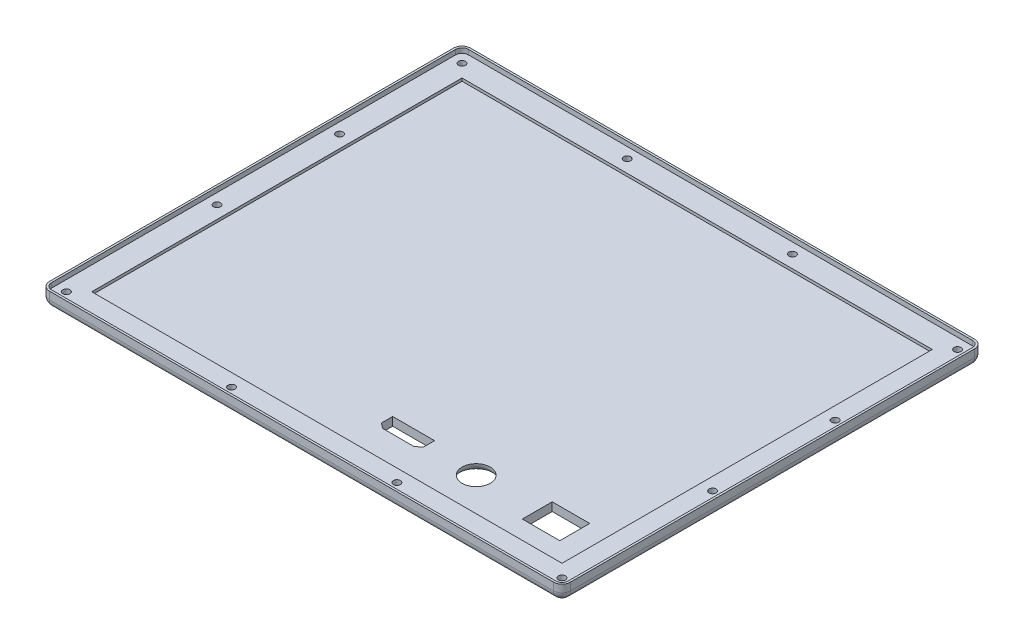
SolidWorks part; units mm, degrees
ref_plane "Front Plane" through (0, 0, 0) normal (0, 0, 1) x (1, 0, 0)
ref_plane "Top Plane" through (0, 0, 0) normal (0, 1, 0) x (1, 0, 0)
ref_plane "Right Plane" through (0, 0, 0) normal (1, 0, 0) x (0, 0, -1)
sketch "Sketch1" plane through (0, 0, 0) normal (0, 1, 0) x (1, 0, 0)
  line L1 (0, 0) -> (164.87, 0)
  line L2 (0, 0) -> (0, -104.3)
  line L3 (0, -104.3) -> (164.87, -104.3)
  line L4 (164.87, 0) -> (164.87, -104.3)
  line L5 (7.23, -7.46) -> (162.2, -7.46)
  line L6 (7.23, -7.46) -> (7.23, -101.93)
  line L7 (7.23, -101.93) -> (162.2, -101.93)
  line L8 (162.2, -7.46) -> (162.2, -101.93)
  line L9 (-4.77, 7.54) -> (174.2, 7.54)
  line L10 (-7.77, 4.54) -> (-7.77, -138.93)
  line L11 (-4.77, -141.93) -> (174.2, -141.93)
  line L12 (177.2, 4.54) -> (177.2, -138.93)
  arc A0 (174.2, -141.93) -> (177.2, -138.93) centre (174.2, -138.93) ccw
  arc A1 (-7.77, -138.93) -> (-4.77, -141.93) centre (-4.77, -138.93) ccw
  arc A2 (-4.77, 7.54) -> (-7.77, 4.54) centre (-4.77, 4.54) ccw
  arc A3 (174.2, 7.54) -> (177.2, 4.54) centre (174.2, 4.54) cw
  dimension "D11" = 3
  dimension "D1" = 104.3
  dimension "D2" = 164.87
  dimension "D3" = 2.67
  dimension "D4" = 2.37
  dimension "D5" = 7.46
  dimension "D6" = 7.23
  dimension "D7" = 15
  dimension "D8" = 15
  dimension "D9" = 15
  dimension "D10" = 40
extrude "Boss-Extrude1" add sketch "Sketch1" against normal blind 1 contours A3 L9 A2 L10 A1 L11 A0 L12 L1 L4 L3 L2 | L4 L1 L2 L3 L5 L8 L7 L6 | L8 L5 L6 L7 region at (82.435, 0, 1.9509) region at (84.715, 0, 54.695) region at (84.715, 0, -5.1619)
sketch "Sketch12" plane through (0, -1, 0) normal (0, -1, 0) x (1, 0, 0)
  line L0 (-4.77, -7.54) -> (174.2, -7.54)
  line L1 (177.2, -4.54) -> (177.2, 138.93)
  line L2 (-4.77, 141.93) -> (174.2, 141.93)
  line L3 (-7.77, -4.54) -> (-7.77, 138.93)
  line L4 (176.45, -4.54) -> (176.45, 138.93)
  line L5 (-4.77, 141.18) -> (174.2, 141.18)
  line L6 (-7.02, -4.54) -> (-7.02, 138.93)
  line L7 (-4.77, -6.79) -> (174.2, -6.79)
  line L8 (176.2, -4.54) -> (176.2, 138.93)
  line L9 (-4.77, -6.54) -> (174.2, -6.54)
  line L10 (176.2, -4.54) -> (176.2, 138.93)
  line L11 (-4.77, -6.54) -> (174.2, -6.54)
  line L18 (-6.77, -4.54) -> (-6.77, 138.93)
  line L19 (-4.77, 140.93) -> (174.2, 140.93)
  line L20 (-6.77, -4.54) -> (-6.77, 138.93)
  line L21 (-4.77, 140.93) -> (174.2, 140.93)
  arc A0 (174.2, -7.54) -> (177.2, -4.54) centre (174.2, -4.54) ccw
  arc A1 (177.2, 138.93) -> (174.2, 141.93) centre (174.2, 138.93) ccw
  arc A2 (-4.77, 141.93) -> (-7.77, 138.93) centre (-4.77, 138.93) ccw
  arc A3 (-7.77, -4.54) -> (-4.77, -7.54) centre (-4.77, -4.54) ccw
  arc A4 (176.45, 138.93) -> (174.2, 141.18) centre (174.2, 138.93) ccw
  arc A5 (-4.77, 141.18) -> (-7.02, 138.93) centre (-4.77, 138.93) ccw
  arc A6 (176.2, 138.93) -> (174.2, 140.93) centre (174.2, 138.93) ccw
  arc A7 (174.2, -6.54) -> (176.2, -4.54) centre (174.2, -4.54) ccw
  arc A8 (176.2, 138.93) -> (174.2, 140.93) centre (174.2, 138.93) ccw
  arc A9 (174.2, -6.54) -> (176.2, -4.54) centre (174.2, -4.54) ccw
  arc A10 (-7.02, -4.54) -> (-4.77, -6.79) centre (-4.77, -4.54) ccw
  arc A11 (174.2, -6.79) -> (176.45, -4.54) centre (174.2, -4.54) ccw
  arc A14 (-6.77, -4.54) -> (-4.77, -6.54) centre (-4.77, -4.54) ccw
  arc A15 (-4.77, 140.93) -> (-6.77, 138.93) centre (-4.77, 138.93) ccw
  arc A16 (-6.77, -4.54) -> (-4.77, -6.54) centre (-4.77, -4.54) ccw
  arc A17 (-4.77, 140.93) -> (-6.77, 138.93) centre (-4.77, 138.93) ccw
  arc M25 (174.2, -7.54) -> (177.2, -4.54) centre (174.2, -4.54) ccw
  line M26 (177.2, -4.54) -> (177.2, 138.93)
  arc M27 (177.2, 138.93) -> (174.2, 141.93) centre (174.2, 138.93) ccw
  line M28 (174.2, 141.93) -> (-4.77, 141.93)
  arc M29 (-4.77, 141.93) -> (-7.77, 138.93) centre (-4.77, 138.93) ccw
  line M30 (-7.77, 138.93) -> (-7.77, -4.54)
  arc M31 (-7.77, -4.54) -> (-4.77, -7.54) centre (-4.77, -4.54) ccw
  line M32 (-4.77, -7.54) -> (174.2, -7.54)
  dimension "D1" = 1
  dimension "D2" = 1
  dimension "D3" = 1
  dimension "D4" = 0.25
sketch "Sketch8" plane through (0, -1, 0) normal (0, -1, 0) x (1, 0, 0)
  line L0 (177.2, -4.54) -> (177.2, 138.93) construction
  line L1 (86.11, 110.85) -> (164.87, 110.85)
  line L2 (86.11, 110.85) -> (86.11, 129.3)
  line L3 (86.11, 129.3) -> (164.87, 129.3)
  line L4 (164.87, 110.85) -> (164.87, 129.3)
  line L5 (-4.77, 141.93) -> (174.2, 141.93) construction
  dimension "D1" = 78.76
  dimension "D2" = 18.45
  dimension "D3" = 12.33
  dimension "D4" = 12.63
sketch "Sketch2" plane through (0, -1, 0) normal (0, -1, 0) x (1, 0, 0)
  line L0 (-7.77, -4.54) -> (-7.77, 138.93) construction
  line L1 (-4.77, -7.54) -> (174.2, -7.54) construction
  line L2 (177.2, -4.54) -> (177.2, 138.93) construction
  line L3 (-4.77, 141.93) -> (174.2, 141.93) construction
  circle A0 centre (-3.27, -3.04) radius 1.25
  circle A1 centre (172.7, -3.04) radius 1.25
  circle A2 centre (172.7, 137.43) radius 1.25
  circle A3 centre (-3.27, 137.43) radius 1.25
  circle A4 centre (-3.27, 40.45) radius 1.25
  circle A5 centre (-3.27, 83.94) radius 1.25
  circle A6 centre (172.7, 40.45) radius 1.25
  circle A7 centre (172.7, 83.94) radius 1.25
  circle A8 centre (114.05, -3.04) radius 1.25
  circle A9 centre (55.38, -3.04) radius 1.25
  circle A10 centre (114.05, 137.43) radius 1.25
  circle A11 centre (55.38, 137.43) radius 1.25
  dimension "D1" = 2.5
  dimension "D4" = 2.5
  dimension "D6" = 2.5
  dimension "D8" = 2.5
  dimension "D9" = 2.5
  dimension "D10" = 2.5
  dimension "D13" = 2.5
  dimension "D14" = 2.5
  dimension "D17" = 2.5
  dimension "D18" = 2.5
  dimension "D19" = 2.5
  dimension "D20" = 2.5
  dimension "D2" = 4.5
  dimension "D3" = 4.5
  dimension "D5" = 4.5
  dimension "D7" = 4.5
  dimension "D11" = 43.49
  dimension "D12" = 43.49
  dimension "D21" = 58.65
  dimension "D22" = 58.65
extrude "Cut-Extrude3" cut sketch "Sketch2" against normal up to next contours A1 | A8 | A0 | A5 | A3 | A11 | A10 | A2 | A7 | A6 | A9 | A4 region at (-3.27, -1, -3.04) region at (172.7, -1, -3.04) region at (172.7, -1, 137.43) region at (-3.27, -1, 137.43) region at (-3.27, -1, 83.94) region at (172.7, -1, 40.45) region at (172.7, -1, 83.94) region at (114.05, -1, -3.04) region at (114.05, -1, 137.43) region at (55.38, -1, 137.43)
extrude "Boss-Extrude2" add sketch "Sketch12" against normal blind 1.7 from surface contours A11 L7 A10 L6 A5 L5 A4 L4 M32 M25 M26 M27 M28 M29 M30 M31 region at (-6.7232, -1, -6.4932) starting at face at (172.7, 0, 85.19)
sketch "Sketch13" plane through (0, -1, 0) normal (0, -1, 0) x (1, 0, 0)
  line L0 (-4.77, -7.54) -> (174.2, -7.54) construction
  line L1 (168.2, 1.46) -> (1.23, 1.46)
  line L2 (168.2, 1.46) -> (168.2, 132.93)
  line L3 (168.2, 132.93) -> (1.23, 132.93)
  line L4 (1.23, 1.46) -> (1.23, 132.93)
  line L5 (177.2, -4.54) -> (177.2, 138.93) construction
  line L6 (-4.77, 141.93) -> (174.2, 141.93) construction
  line L7 (-7.77, -4.54) -> (-7.77, 138.93) construction
  dimension "D1" = 9
  dimension "D2" = 9
  dimension "D3" = 9
  dimension "D4" = 9
extrude "Cut-Extrude4" cut sketch "Sketch13" against normal up to next
extrude "Boss-Extrude3" add sketch "Sketch1<4>" against normal blind 3 from surface contours A3 L9 A2 L10 A1 L11 A0 L12 L1 L4 L3 L2 | L4 L1 L2 L3 L5 L8 L7 L6 | L8 L5 L6 L7 region at (82.435, 0, 1.9509) region at (84.715, 0, 54.695) region at (84.715, 0, -5.1619) starting at face at (84.715, -1, 67.195)
sketch "Sketch1<4>" plane through (0, 0, 0) normal (0, 1, 0) x (1, 0, 0) same geometry as "Sketch1"
fillet "Fillet1" radius 3 8 edges at (176.3213, -4, -6.6613) (84.715, -4, -7.54) (-6.8913, -4, -6.6613) (-7.77, -4, 67.195) (-6.8913, -4, 141.0513) (84.715, -4, 141.93) (176.3213, -4, 141.0513) (177.2, -4, 67.195)
sketch "Sketch15" plane through (0, -4, 0) normal (0, -1, 0) x (1, 0, 0)
  line L0 (106.87, 116.85) -> (92.01, 116.85)
  line L1 (86.11, 110.85) -> (164.87, 110.85) construction
  line L2 (92.01, 116.85) -> (92.01, 120.92)
  line L3 (164.87, 110.85) -> (164.87, 129.3) construction
  line L4 (159.87, 114.765) -> (146.56, 114.765)
  line L5 (159.87, 114.765) -> (159.87, 125.375)
  line L6 (159.87, 125.375) -> (146.56, 125.375)
  line L7 (146.56, 114.765) -> (146.56, 125.375)
  line L8 (86.11, 129.3) -> (164.87, 129.3) construction
  line L13 (106.87, 116.85) -> (106.87, 120.92)
  line L14 (106.87, 120.92) -> (104.87, 122.3)
  line L15 (104.87, 122.3) -> (94.01, 122.3)
  line L16 (94.01, 122.3) -> (92.01, 120.92)
  line L17 (86.11, 110.85) -> (86.11, 129.3) construction
  circle A0 centre (124.87, 120.075) radius 5
  dimension "D1" = 10
  dimension "D2" = 9.225
  dimension "D3" = 40
  dimension "D4" = 10.61
  dimension "D5" = 13.31
  dimension "D6" = 5
  dimension "D7" = 3.925
  dimension "D8" = 4.07
  dimension "D9" = 10.86
  dimension "D10" = 14.86
  dimension "D11" = 5.45
  dimension "D12" = 2
  dimension "D13" = 5.9
  dimension "D14" = 6
extrude "Cut-Extrude5" cut sketch "Sketch15" against normal up to next
fillet "Fillet2" radius 3 1 edges at (124.87, -4, 115.075)
sketch "Sketch16" plane through (0, -4, 0) normal (0, -1, 0) x (1, 0, 0)
  line L1 (174.2, -4.54) -> (174.2, 138.93) construction
  line L2 (-4.77, -4.54) -> (174.2, -4.54) construction
  line L3 (81.3952, 54.71) -> (88.0348, 54.71)
  line L4 (81.5396, 54.96) -> (87.8904, 54.96)
  line L5 (87.8904, 54.96) -> (91.0659, 60.46)
  line L6 (91.0659, 60.46) -> (87.8904, 65.96)
  line L7 (87.8904, 65.96) -> (81.5396, 65.96)
  line L8 (81.5396, 65.96) -> (78.3641, 60.46)
  line L9 (78.3641, 60.46) -> (81.5396, 54.96)
  line L10 (88.0348, 54.71) -> (91.3545, 60.46)
  line L11 (91.3545, 60.46) -> (88.0348, 66.21)
  line L12 (88.0348, 66.21) -> (81.3952, 66.21)
  line L13 (81.3952, 66.21) -> (78.0755, 60.46)
  line L14 (78.0755, 60.46) -> (81.3952, 54.71)
  circle A0 centre (84.715, 60.46) radius 3.9497
  circle A1 centre (84.715, 60.46) radius 5.5 construction
  circle A2 centre (84.715, 60.46) radius 17.5
  circle A3 centre (84.715, 60.46) radius 20.5
  dimension "D2" = 7.8994
  dimension "D5" = 11
  dimension "D6" = 35
  dimension "D1" = 89.485
  dimension "D3" = 65
  dimension "D4" = 0.25
  dimension "D7" = 3
extrude "Boss-Extrude4" add sketch "Sketch16" along normal blind 7 contours A3 | L3 L10 L11 L12 L13 L14
extrude "Boss-Extrude5" add sketch "Sketch16<3>" along normal blind 3 from surface contours A3 A2 region at (64.7948, -4, 60.46) starting at face at (84.715, -11, 39.96)
sketch "Sketch16<3>" plane through (0, -4, 0) normal (0, -1, 0) x (1, 0, 0) same geometry as "Sketch16"
fillet "Fillet3" radius 10 1 edges at (84.715, -4, 80.96)
sketch "Sketch17" plane through (0, -4, 0) normal (0, -1, 0) x (-1, 0, 0)
  text T0 "12V" font "DejaVu Sans Mono" height 6
  text T1 "HDMI" font "DejaVu Sans Mono" height 6
  text T2 "Composite\r\n Video" font "DejaVu Sans Mono" height 5
extrude "Boss-Extrude6" add sketch "Sketch17" along normal blind 2
extrude "Cut-Extrude6" cut sketch "Sketch2<7>" along normal up to next
sketch "Sketch2<7>" plane through (0, -1, 0) normal (0, -1, 0) x (1, 0, 0) same geometry as "Sketch2"
